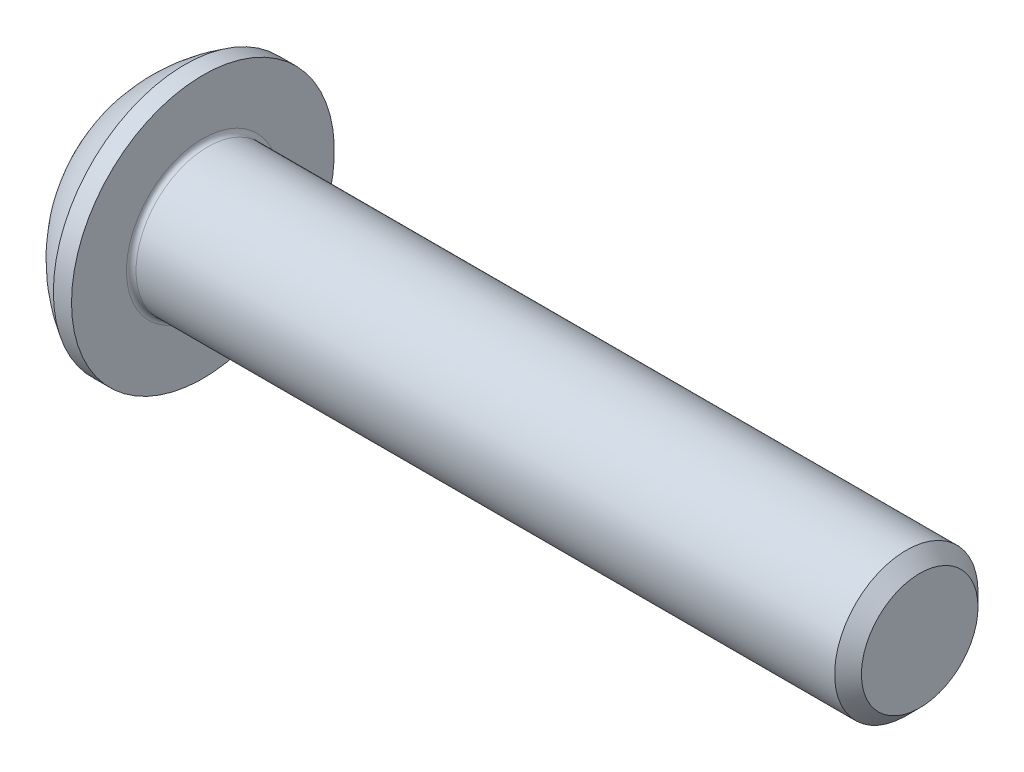
SolidWorks part; units mm, degrees
material "Plain Carbon Steel"
ref_plane "Front Plane" through (0, 0, 0) normal (0, 0, 1) x (1, 0, 0)
ref_plane "Top Plane" through (0, 0, 0) normal (0, 1, 0) x (1, 0, 0)
ref_plane "Right Plane" through (0, 0, 0) normal (1, 0, 0) x (0, 0, -1)
ref_plane "Plane1" through (0, 0, 0) normal (0, 0, -1) x (-1, 0, 0)
sketch "Sketch1" plane through (0, 0, 0) normal (0, 0, -1) x (-1, 0, 0)
  line L0 (-1.65, 2.75) -> (-1.65, 0)
  line L1 (-1.65, 0) -> (0, 0)
  line L2 (0, 0) -> (0, 1.425)
  line L3 (-1.27, 2.75) -> (-1.65, 2.75)
  line L4 (-1.65, 0) -> (0, 0) construction
  arc A0 (0, 1.425) -> (-1.27, 2.75) centre (-2.962, -0.1429) ccw
  dimension "D5" = 3.3514
  dimension "D1" = 2.75
  dimension "D2" = 1.65
  dimension "D3" = 1.425
  dimension "D4" = 0.38
revolve "Revolve1" add sketch "Sketch1" angle 360 about L4 reverse direction yes
sketch "Sketch2" plane through (0, 0, 0) normal (-1, 0, 0) x (0, 0, 1)
  line L7 (-1, 0.5774) -> (-1, -0.5774)
  line L8 (-1, -0.5774) -> (0, -1.1547)
  line L9 (0, -1.1547) -> (1, -0.5774)
  line L10 (1, -0.5774) -> (1, 0.5774)
  line L11 (1, 0.5774) -> (0, 1.1547)
  line L12 (0, 1.1547) -> (-1, 0.5774)
  circle A0 centre (0, 0) radius 1 construction
  dimension "D1" = 2
extrude "Cut-Extrude1" cut sketch "Sketch2" against normal blind 1.04
sketch "Sketch3" plane through (0, 0, 0) normal (0, 0, 1) x (1, 0, 0)
  line L0 (1.04, 1) -> (1.04, 0)
  line L1 (1.04, 0) -> (1.6174, 0)
  line L2 (1.6174, 0) -> (1.04, 1)
  line L3 (1.04, 0) -> (1.6174, 0) construction
revolve "Cut-Revolve1" cut sketch "Sketch3" angle 360 about L3 reverse direction yes
sketch "Sketch4" plane through (1.65, 0, 0) normal (1, 0, 0) x (0, 0, -1)
  circle A0 centre (0, 0) radius 1.5
extrude "Largo y Ancho rosca" add sketch "Sketch4" along normal blind 15
fillet "Fillet1" radius 0.1 1 edges at (1.65, 0, -1.5) tangent propagation no
chamfer "Chamfer1" distance 0.2805 angle 45 1 edges at (16.65, 0, -1.5)
